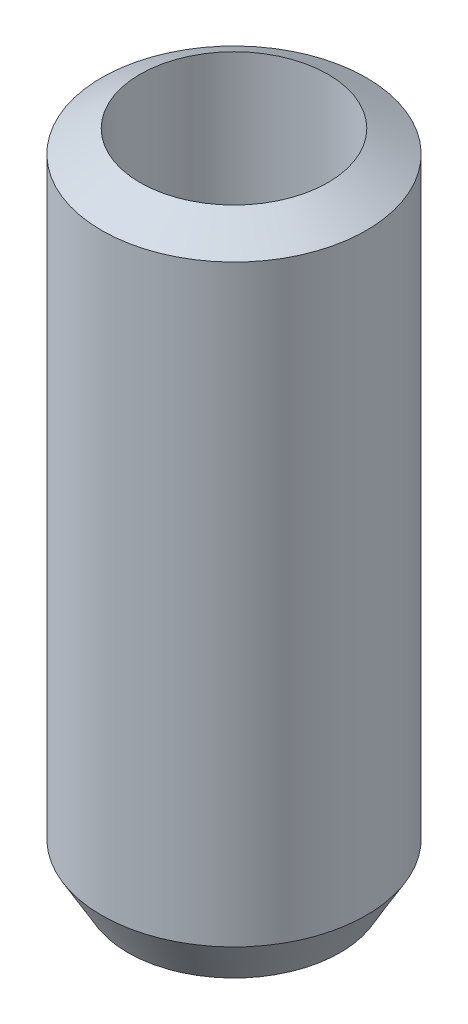
SolidWorks part; units mm, degrees
ref_plane "Front Plane" through (0, 0, 0) normal (0, 0, 1) x (1, 0, 0)
ref_plane "Top Plane" through (0, 0, 0) normal (0, 1, 0) x (1, 0, 0)
ref_plane "Right Plane" through (0, 0, 0) normal (1, 0, 0) x (0, 0, -1)
sketch "Sketch1" plane through (0, 0, 0) normal (0, 1, 0) x (1, 0, 0)
  circle A0 centre (0, 0) radius 17.5
  dimension "SHAFT_OD" = 35
extrude "Boss-Extrude1" add sketch "Sketch1" along normal blind 87.9081
sketch "Sketch2" plane through (0, 0, 0) normal (0, 1, 0) x (1, 0, 0)
  circle A0 centre (0, 0) radius 12.4188
  dimension "BORE_D" = 24.8376
extrude "Cut-Extrude1" cut sketch "Sketch2" along normal through all
chamfer "Chamfer1" distance 3.4699 angle 60 2 edges at (0, 87.9081, 17.5) (0, 0, 17.5) first distance on face at (0, 87.9081, 17.5) first distance on face at (0, 0, 12.4188)
